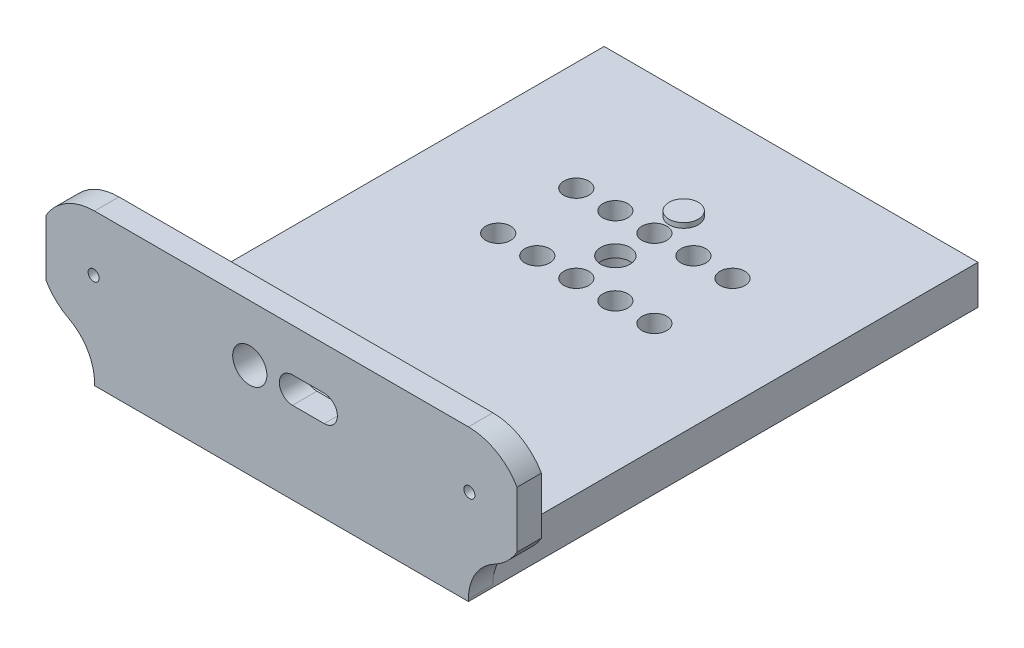
SolidWorks part; units mm, degrees
ref_plane "正面" through (0, 0, 0) normal (0, 0, 1) x (1, 0, 0)
ref_plane "平面" through (0, 0, 0) normal (0, 1, 0) x (1, 0, 0)
ref_plane "右側面" through (0, 0, 0) normal (1, 0, 0) x (0, 0, -1)
sketch "ｽｹｯﾁ1" plane through (0, 0, 0) normal (0, 1, 0) x (1, 0, 0)
  line L0 (0, 49.7) -> (0, 0) construction
  line L1 (-38.3, 49.7) -> (38.3, 49.7)
  line L2 (-38.3, 49.7) -> (-38.3, -49.7)
  line L3 (-38.3, -49.7) -> (38.3, -49.7)
  line L4 (38.3, 49.7) -> (38.3, -49.7)
  line L5 (-38.3, 49.7) -> (38.3, -49.7) construction
  line L6 (-38.3, -49.7) -> (38.3, 49.7) construction
  circle A0 centre (0, 13.7) radius 3
  point P0 (0, 0)
  dimension "D3" = 6
  dimension "D1" = 76.6
  dimension "D2" = 99.4
  dimension "D4" = 36
extrude "ﾎﾞｽ - 押し出し1" add sketch "ｽｹｯﾁ1" along normal blind 8
sketch "ｽｹｯﾁ2" plane through (0, 0, 0) normal (0, -1, 0) x (1, 0, 0)
  circle A0 centre (0, -13.7) radius 3 construction
  circle A1 centre (0, -13.7) radius 3 construction
  circle A2 centre (0, -13.7) radius 4.5
  dimension "D1" = 9
extrude "ｶｯﾄ - 押し出し1" cut sketch "ｽｹｯﾁ2" against normal blind 5.5
sketch "ｽｹｯﾁ3" plane through (0, 8, 0) normal (0, 1, 0) x (1, 0, 0)
  line L0 (0, 49.7) -> (0, 0) construction
  line L1 (38.3, 49.7) -> (-38.3, 49.7) construction
  circle A0 centre (0, 27.7) radius 3
  dimension "D1" = 6
  dimension "D2" = 22
extrude "ﾎﾞｽ - 押し出し2" add sketch "ｽｹｯﾁ3" along normal blind 1
sketch "ｽｹｯﾁ5" plane through (0, 8, 0) normal (0, 1, 0) x (1, 0, 0)
  line L0 (-38.3, 13.7) -> (38.3, 13.7) construction
  line L1 (-38.3, 49.7) -> (-38.3, -49.7) construction
  line L2 (38.3, -49.7) -> (38.3, 49.7) construction
  line L3 (0, 49.7) -> (0, -49.7) construction
  line L4 (38.3, 49.7) -> (-38.3, 49.7) construction
  line L5 (-38.3, -49.7) -> (38.3, -49.7) construction
  circle A0 centre (0, 13.7) radius 3 construction
  circle A1 centre (0, 21.7) radius 1.05
  circle A2 centre (8, 21.7) radius 1.05
  circle A3 centre (16, 21.7) radius 1.05
  circle A4 centre (-8, 21.7) radius 1.05
  circle A5 centre (-16, 21.7) radius 1.05
  circle A6 centre (-16, 5.7) radius 1.05
  circle A7 centre (-8, 5.7) radius 1.05
  circle A8 centre (16, 5.7) radius 1.05
  circle A9 centre (8, 5.7) radius 1.05
  circle A10 centre (0, 5.7) radius 1.05
  point P12 (0, 13.7)
  dimension "D1" = 2.1
  dimension "D2" = 8
  dimension "D3" = 3
  dimension "D4" = 3
extrude "ｶｯﾄ - 押し出し2" cut sketch "ｽｹｯﾁ5" against normal through all
sketch "ｽｹｯﾁ6" plane through (0, 8, 0) normal (0, 1, 0) x (1, 0, 0)
  circle A86 centre (-8, 21.7) radius 2.55
  circle A87 centre (-16, 21.7) radius 2.55
  circle A88 centre (-16, 21.7) radius 2.55
  circle A89 centre (0, 21.7) radius 2.55
  circle A90 centre (8, 21.7) radius 2.55
  circle A91 centre (16, 21.7) radius 2.55
  circle A92 centre (-8, 5.7) radius 2.55
  circle A93 centre (0, 5.7) radius 2.55
  circle A94 centre (8, 5.7) radius 2.55
  circle A95 centre (16, 5.7) radius 2.55
  circle A96 centre (-16, 5.7) radius 2.55
  dimension "D1" = 1.5
  dimension "D2" = 5
  dimension "D3" = 2
extrude "ｶｯﾄ - 押し出し3" cut sketch "ｽｹｯﾁ6" against normal blind 5
sketch "ｽｹｯﾁ7" plane through (0, 0, 49.7) normal (0, 0, 1) x (1, 0, 0)
  line L0 (8.75, 21.2) -> (2.25, 21.2) construction
  line L1 (2.25, 17.8) -> (8.75, 17.8) construction
  line L2 (8.75, 21.2) -> (2.25, 21.2) construction
  line L3 (2.25, 17.8) -> (8.75, 17.8) construction
  line L4 (-38.3, 0) -> (38.3, 0)
  line L5 (38.3, 0) -> (38.3, 8)
  line L6 (38.3, 8) -> (-38.3, 8)
  line L7 (-38.3, 8) -> (-38.3, 0)
  line L8 (-38.3, 0) -> (38.3, 0)
  line L9 (38.3, 0) -> (38.3, 8)
  line L11 (-38.3, 8) -> (-38.3, 0)
  line L12 (48.25, 13.7339) -> (48.25, 25.2661)
  line L13 (38.3, 31) -> (-38.3, 31)
  line L14 (-48.25, 25.2661) -> (-48.25, 13.7339)
  line L15 (-38.3, 8) -> (38.3, 8)
  line L16 (48.25, 13.7339) -> (48.25, 25.2661)
  line L17 (38.3, 31) -> (-38.3, 31)
  line L18 (-48.25, 25.2661) -> (-48.25, 13.7339)
  line L19 (2.25, 16.8) -> (8.75, 16.8)
  line L20 (8.75, 22.2) -> (2.25, 22.2)
  arc A0 (2.25, 21.2) -> (2.25, 17.8) centre (2.25, 19.5) ccw construction
  arc A1 (8.75, 17.8) -> (8.75, 21.2) centre (8.75, 19.5) ccw construction
  circle A2 centre (-6.5, 19.5) radius 2.5 construction
  arc A3 (2.25, 21.2) -> (2.25, 17.8) centre (2.25, 19.5) ccw construction
  arc A4 (48.25, 25.2661) -> (38.3, 31) centre (38.3, 19.5) ccw
  arc A5 (-38.3, 31) -> (-48.25, 25.2661) centre (-38.3, 19.5) ccw
  arc A6 (-48.25, 13.7339) -> (-38.3, 8) centre (-38.3, 19.5) ccw
  arc A7 (38.3, 8) -> (48.25, 13.7339) centre (38.3, 19.5) ccw
  arc A8 (48.25, 25.2661) -> (38.3, 31) centre (38.3, 19.5) ccw
  arc A9 (-38.3, 31) -> (-48.25, 25.2661) centre (-38.3, 19.5) ccw
  arc A10 (-48.25, 13.7339) -> (-38.3, 8) centre (-38.3, 19.5) ccw
  arc A11 (38.3, 8) -> (48.25, 13.7339) centre (38.3, 19.5) ccw
  arc A12 (8.75, 17.8) -> (8.75, 21.2) centre (8.75, 19.5) ccw construction
  circle A13 centre (-6.5, 19.5) radius 2.5 construction
  circle A14 centre (-6.5, 19.5) radius 3.5
  arc A15 (2.25, 22.2) -> (2.25, 16.8) centre (2.25, 19.5) ccw
  arc A16 (8.75, 16.8) -> (8.75, 22.2) centre (8.75, 19.5) ccw
  circle A17 centre (38.5, 19.5) radius 1.025 construction
  circle A18 centre (-38.5, 19.5) radius 1.025 construction
  circle A19 centre (38.5, 19.5) radius 1.025 construction
  circle A20 centre (-38.5, 19.5) radius 1.025 construction
  circle A21 centre (38.5, 19.5) radius 1.125
  circle A22 centre (-38.5, 19.5) radius 1.125
  dimension "D1" = 0
  dimension "D2" = 0
  dimension "D3" = 1
  dimension "D4" = 0.1
extrude "ﾎﾞｽ - 押し出し3" add sketch "ｽｹｯﾁ7" along normal blind 5
fillet "ﾌｨﾚｯﾄ1" radius 10 2 edges at (38.3, 8, 52.2) (-38.3, 8, 52.2)
